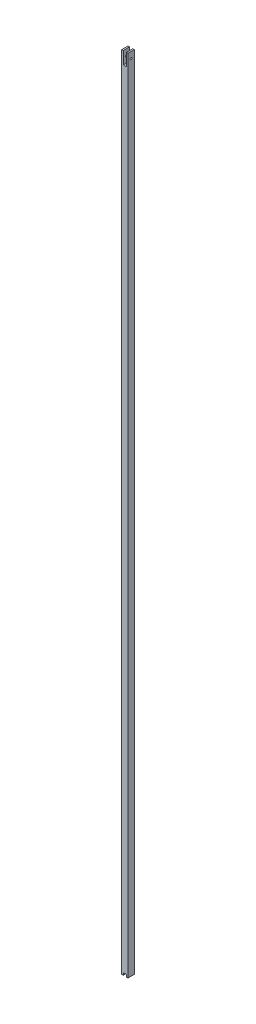
SolidWorks part; units mm, degrees
material "Plain Carbon Steel"
ref_plane "Front Plane" through (0, 0, 0) normal (0, 0, 1) x (1, 0, 0)
ref_plane "Top Plane" through (0, 0, 0) normal (0, 1, 0) x (1, 0, 0)
ref_plane "Right Plane" through (0, 0, 0) normal (1, 0, 0) x (0, 0, -1)
sketch "Sketch1" plane through (0, 0, 0) normal (0, 0, 1) x (1, 0, 0)
  line L0 (0, 0) -> (1.5875, 0)
  line L1 (1.5875, 0) -> (1.5875, 2.3812)
  line L2 (1.5875, 2.3812) -> (4.7625, 2.3812)
  line L3 (4.7625, 2.3812) -> (4.7625, 0)
  line L4 (4.7625, 0) -> (6.35, 0)
  line L5 (6.35, 0) -> (6.35, 812.8)
  line L6 (6.35, 812.8) -> (4.7625, 812.8)
  line L7 (4.7625, 812.8) -> (4.7625, 800.1)
  line L8 (4.7625, 800.1) -> (1.5875, 800.1)
  line L9 (1.5875, 800.1) -> (1.5875, 812.8)
  line L10 (1.5875, 812.8) -> (0, 812.8)
  line L11 (0, 812.8) -> (0, 0)
  dimension "D1" = 1.5875
  dimension "D2" = 2.3812
  dimension "D3" = 3.175
  dimension "D4" = 2.3812
  dimension "D5" = 1.5875
  dimension "D6" = 812.8
  dimension "D7" = 1.5875
  dimension "D8" = 12.7
  dimension "D9" = 3.175
  dimension "D10" = 12.7
extrude "Boss-Extrude1" add sketch "Sketch1" along normal blind 6.35
sketch "Sketch2" plane through (0, 0, 0) normal (1, 0, 0) x (0, 0, -1)
  circle A0 centre (3.175, 806.45) radius 1
  dimension "D1" = 2
sketch "Sketch3" plane through (0, 0, 0) normal (1, 0, 0) x (0, 0, -1)
  circle A0 centre (-3.175, 806.45) radius 1
  dimension "D1" = 2
extrude "Cut-Extrude3" cut sketch "Sketch3" against normal mid plane 20
